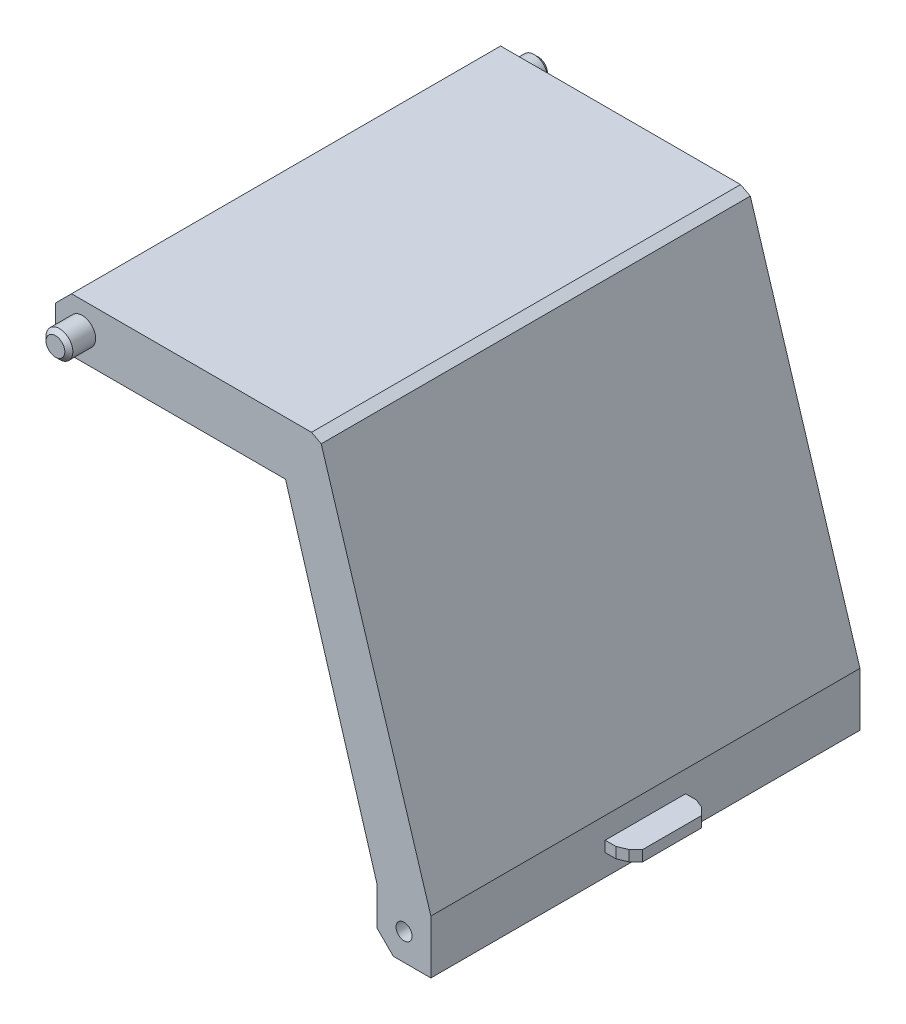
SolidWorks part; units mm, degrees
ref_plane "Front Plane" through (0, 0, 0) normal (0, 0, 1) x (1, 0, 0)
ref_plane "Top Plane" through (0, 0, 0) normal (0, 1, 0) x (1, 0, 0)
ref_plane "Right Plane" through (0, 0, 0) normal (1, 0, 0) x (0, 0, -1)
sketch "Sketch1" plane through (0, 0, 0) normal (0, 0, 1) x (1, 0, 0)
  line L0 (-5, 5) -> (-22.101, 61.9846)
  line L1 (-5, -5) -> (5, -5)
  line L2 (-5, -5) -> (-5, 5)
  line L3 (-5, 5) -> (5, 5)
  line L4 (5, -5) -> (5, 5)
  line L5 (-5, -5) -> (5, 5) construction
  line L6 (-5, 5) -> (5, -5) construction
  line L7 (5, 5) -> (-12.5931, 61.819)
  line L8 (-12.5931, 61.819) -> (-15.7407, 71.9846)
  line L13 (-15.7407, 71.9846) -> (-22.101, 71.9846)
  line L15 (-22.101, 71.9846) -> (-32.101, 71.9846)
  line L16 (-22.101, 71.9846) -> (-22.101, 61.9846)
  line L17 (-22.101, 61.9846) -> (-32.101, 61.9846)
  line L18 (-32.101, 71.9846) -> (-32.101, 61.9846)
  line L19 (-32.101, 71.9846) -> (-65.001, 71.9846)
  line L20 (-32.101, 71.9846) -> (-32.101, 61.9846)
  line L21 (-32.101, 61.9846) -> (-65.001, 61.9846)
  line L22 (-65.001, 71.9846) -> (-65.001, 61.9846)
  point P0 (0, 0)
  dimension "D1" = 10
  dimension "D2" = 10
  dimension "D3" = 10
  dimension "D4" = 32.9
extrude "Boss-Extrude1" add sketch "Sketch1" along normal blind 80 contours L15 | L8 L13 L3 L7 | L1 L4 L3 L2 | L19 L22 L21 L18 region at (0, 0, 0) region at (-9.7904, 37.4009, 0) region at (-27.101, 66.9846, 0) region at (-48.551, 66.9846, 0)
chamfer "Chamfer1" distance 3 angle 45 1 edges at (-5, -5, 40)
sketch "Sketch2" plane through (0, 0, 80) normal (0, 0, 1) x (1, 0, 0)
  line L0 (-65.001, 66.9846) -> (-60.001, 66.9846)
  line L1 (-65.001, 71.9846) -> (-65.001, 61.9846) construction
  circle A1 centre (-60.001, 66.9846) radius 2.5
extrude "Boss-Extrude2" add sketch "Sketch2" along normal blind 5 from surface contours A1 starting at face at (-18.8715, 29.5487, 80)
extrude "Boss-Extrude3" add sketch "Sketch2<2>" against normal blind 5 from surface contours A1 starting at face at (-18.8715, 29.5487, 0)
sketch "Sketch2<2>" plane through (0, 0, 80) normal (0, 0, 1) x (1, 0, 0) same geometry as "Sketch2"
chamfer "Chamfer2" distance 1 angle 45 1 edges at (-15.7407, 71.9846, 40) first distance on face at (-5.3704, 38.4923, 40)
chamfer "Chamfer3" distance 0.75 angle 45 2 edges at (-57.501, 66.9846, -5) (-57.501, 66.9846, 85)
sketch "Sketch3" plane through (5, 0, 0) normal (1, 0, 0) x (0, 0, -1)
  line L0 (-40, -5) -> (-40, 0)
  line L1 (-80, -5) -> (0, -5) construction
  line L3 (-47.5, -1) -> (-32.5, -1)
  line L4 (-47.5, -1) -> (-47.5, 1)
  line L5 (-47.5, 1) -> (-32.5, 1)
  line L6 (-32.5, -1) -> (-32.5, 1)
  line L7 (-47.5, -1) -> (-32.5, 1) construction
  line L8 (-47.5, 1) -> (-32.5, -1) construction
  dimension "D1" = 15
  dimension "D2" = 2
extrude "Boss-Extrude4" add sketch "Sketch3" along normal blind 5 contours L5 L6 L3 L4
chamfer "Chamfer4" distance 2 angle 45 2 edges at (10, 0, 32.5) (10, 0, 47.5)
chamfer "Chamfer5" distance 1 angle 22.5 2 edges at (8, 0, 32.5) (8, 0, 47.5) first distance on face at (9, 0, 33.5) first distance on face at (9, 0, 46.5)
chamfer "Chamfer6" distance 3 angle 45 2 edges at (-65.001, 71.9846, 40) (-65.001, 61.9846, 40)
sketch "Sketch4" plane through (0, 0, 80) normal (0, 0, 1) x (1, 0, 0)
  line L1 (5, -5) -> (0, -5)
  line L2 (5, -5) -> (5, 0)
  line L3 (5, 0) -> (0, 0)
  line L4 (0, -5) -> (0, 0)
  circle A0 centre (0, 0) radius 1.5
extrude "Cut-Extrude1" cut sketch "Sketch4" against normal blind 5 contours A0
extrude "Cut-Extrude2" cut sketch "Sketch4<3>" along normal blind 5 from surface contours A0 starting at face at (-57.501, 66.9846, 0)
sketch "Sketch4<3>" plane through (0, 0, 80) normal (0, 0, 1) x (1, 0, 0) same geometry as "Sketch4"
sketch "Sketch5" plane through (5.9753, 1.8502, 0) normal (0.9553, 0.2958, 0) x (0, 0, -1)
  line L0 (0, 72.4195) -> (-80, 72.4195) construction
  line L1 (-80, 3.2974) -> (-80, 72.4195) construction
  line L2 (-40, 20.0585) -> (-40, 17.6907)
  line L3 (-51.5, 29.3012) -> (-28.5, 29.3012)
  line L4 (-51.5, 29.3012) -> (-51.5, 10.8157)
  line L5 (-51.5, 10.8157) -> (-28.5, 10.8157)
  line L6 (-28.5, 29.3012) -> (-28.5, 10.8157)
  line L7 (-51.5, 29.3012) -> (-28.5, 10.8157) construction
  line L8 (-51.5, 10.8157) -> (-28.5, 29.3012) construction
  line L9 (-40, 20.0585) -> (-40, 10.8157)
  line L10 (-47, 15.8157) -> (-33, 15.8157)
  line L11 (-47, 15.8157) -> (-47, 19.5657)
  line L12 (-47, 19.5657) -> (-33, 19.5657)
  line L13 (-33, 15.8157) -> (-33, 19.5657)
  line L14 (-47, 15.8157) -> (-33, 19.5657) construction
  line L15 (-47, 19.5657) -> (-33, 15.8157) construction
  line L20 (-48.25, 12.1657) -> (-48.25, 13.5657)
  line L26 (-48.25, 12.1657) -> (-31.75, 12.1657)
  line L27 (-48.25, 12.1657) -> (-48.25, 13.5657)
  line L28 (-48.25, 13.5657) -> (-31.75, 13.5657)
  line L29 (-31.75, 12.1657) -> (-31.75, 13.5657)
  circle A0 centre (-40, 37.8585) radius 18.935
  circle A1 centre (-40, 37.8585) radius 17.8
  circle A2 centre (-29.5, 15.8157) radius 0.725
  circle A3 centre (-50.5, 15.8157) radius 0.725
  point P0 (-40, 72.4195)
  point P1 (-80, 37.8585)
  point P4 (-40, 37.8585)
  point P10 (-40, 20.0585)
  point P11 (-40, 20.0585)
  point P16 (-51.5, 22.8157)
  point P17 (-51.5, 22.8157)
  point P27 (-29.5, 15.8157)
  point P30 (-33, 15.8157)
  dimension "D1" = 37.87
  dimension "D2" = 23
  dimension "D8" = 1.45
  dimension "D9" = 1
  dimension "D6" = 5
  dimension "D7" = 3.25
  dimension "D3" = 12
  dimension "D4" = 3.75
  dimension "D5" = 14
  dimension "D10" = 3.25
  dimension "D11" = 16.5
  dimension "D12" = 1.35
